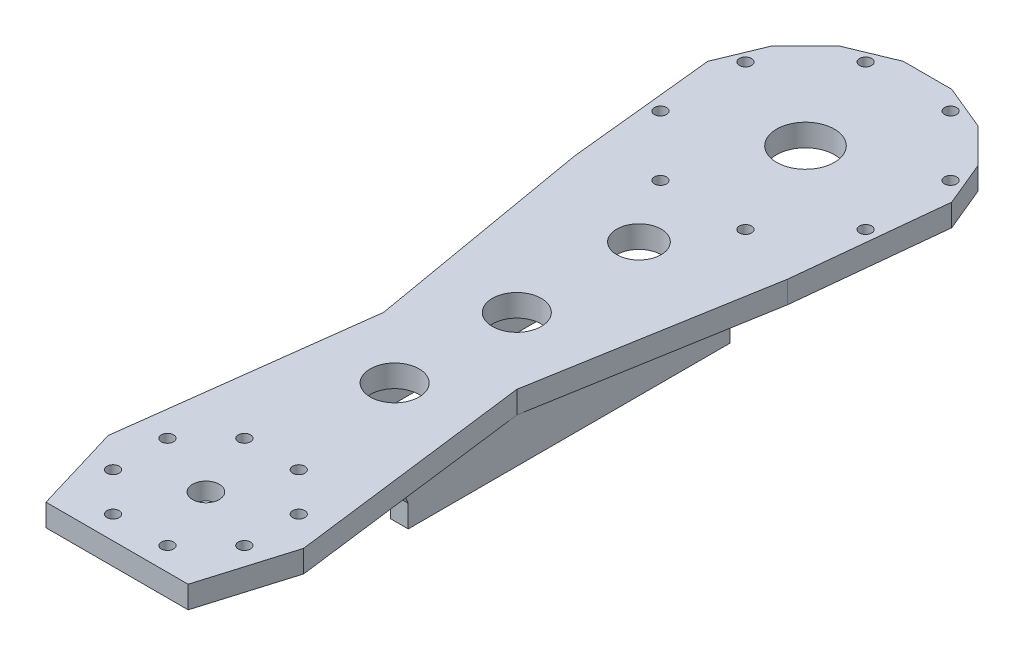
SolidWorks part; units mm, degrees
material "6061-T6 (SS)"
ref_plane "Front Plane" through (0, 0, 0) normal (0, 0, 1) x (1, 0, 0)
ref_plane "Top Plane" through (0, 0, 0) normal (0, 1, 0) x (1, 0, 0)
ref_plane "Right Plane" through (0, 0, 0) normal (1, 0, 0) x (0, 0, -1)
ref_plane "PL_Thigh_Plate_base" through (0, 36, 0) normal (0, 1, 0) x (1, 0, 0)
sketch "SK_Thigh_Plate" plane through (0, 36, 0) normal (0, 1, 0) x (1, 0, 0)
  line L0 (-32, -40) -> (32, -40)
  line L1 (32, -40) -> (44, 0)
  line L2 (44, 0) -> (30, 110)
  line L3 (30, 110) -> (48, 214)
  line L4 (48, 214) -> (54.924, 280.9251)
  line L5 (54.924, 280.9251) -> (46.5623, 301.1119)
  line L6 (46.5623, 301.1119) -> (31.1119, 316.5623)
  line L7 (31.1119, 316.5623) -> (10.9251, 324.924)
  line L8 (10.9251, 324.924) -> (-10.9251, 324.924)
  line L9 (-10.9251, 324.924) -> (-31.1119, 316.5623)
  line L10 (-31.1119, 316.5623) -> (-46.5623, 301.1119)
  line L11 (-46.5623, 301.1119) -> (-54.924, 280.9251)
  line L12 (-54.924, 280.9251) -> (-48, 214)
  line L13 (-48, 214) -> (-30, 110)
  line L14 (-30, 110) -> (-44, 0)
  line L15 (-44, 0) -> (-32, -40)
  circle A0 centre (29.5641, 12.2459) radius 2.75
  circle A1 centre (12.2459, 29.5641) radius 2.75
  circle A2 centre (-12.2459, 29.5641) radius 2.75
  circle A3 centre (-29.5641, 12.2459) radius 2.75
  circle A4 centre (-29.5641, -12.2459) radius 2.75
  circle A5 centre (-12.2459, -29.5641) radius 2.75
  circle A6 centre (12.2459, -29.5641) radius 2.75
  circle A7 centre (29.5641, -12.2459) radius 2.75
  circle A8 centre (46.194, 289.1342) radius 2.75
  circle A9 centre (19.1342, 316.194) radius 2.75
  circle A10 centre (-19.1342, 316.194) radius 2.75
  circle A11 centre (-46.194, 289.1342) radius 2.75
  circle A12 centre (-46.194, 250.8658) radius 2.75
  circle A13 centre (-19.1342, 223.806) radius 2.75
  circle A14 centre (19.1342, 223.806) radius 2.75
  circle A15 centre (46.194, 250.8658) radius 2.75
  circle A16 centre (0, 0) radius 6
  circle A17 centre (0, 270) radius 13
  circle A18 centre (0, 85) radius 11
  circle A19 centre (0, 140) radius 11
  circle A20 centre (0, 195) radius 10
  dimension "D31_SK_Thigh_Plate" = 5.5
  dimension "D34_SK_Thigh_Plate" = 5.5
  dimension "D37_SK_Thigh_Plate" = 5.5
  dimension "D40_SK_Thigh_Plate" = 5.5
  dimension "D43_SK_Thigh_Plate" = 5.5
  dimension "D46_SK_Thigh_Plate" = 5.5
  dimension "D49_SK_Thigh_Plate" = 5.5
  dimension "D52_SK_Thigh_Plate" = 5.5
  dimension "D55_SK_Thigh_Plate" = 5.5
  dimension "D58_SK_Thigh_Plate" = 5.5
  dimension "D61_SK_Thigh_Plate" = 5.5
  dimension "D64_SK_Thigh_Plate" = 5.5
  dimension "D67_SK_Thigh_Plate" = 5.5
  dimension "D70_SK_Thigh_Plate" = 5.5
  dimension "D73_SK_Thigh_Plate" = 5.5
  dimension "D76_SK_Thigh_Plate" = 5.5
  dimension "D79_SK_Thigh_Plate" = 12
  dimension "D80_SK_Thigh_Plate" = 26
  dimension "D82_SK_Thigh_Plate" = 22
  dimension "D84_SK_Thigh_Plate" = 22
  dimension "D86_SK_Thigh_Plate" = 20
  dimension "P1" = 32
  dimension "P2" = 40
  dimension "P3" = 32
  dimension "P4" = 40
  dimension "P5" = 44
  dimension "P6" = 30
  dimension "P7" = 110
  dimension "P8" = 48
  dimension "P9" = 214
  dimension "P10" = 54.924
  dimension "P11" = 280.9251
  dimension "P12" = 46.5623
  dimension "P13" = 301.1119
  dimension "P14" = 31.1119
  dimension "P15" = 316.5623
  dimension "P16" = 10.9251
  dimension "P17" = 324.924
  dimension "P18" = 10.9251
  dimension "P19" = 324.924
  dimension "P20" = 31.1119
  dimension "P21" = 316.5623
  dimension "P22" = 46.5623
  dimension "P23" = 301.1119
  dimension "P24" = 54.924
  dimension "P25" = 280.9251
  dimension "P26" = 48
  dimension "P27" = 214
  dimension "P28" = 30
  dimension "P29" = 110
  dimension "P30" = 44
  dimension "P32" = 29.5641
  dimension "P33" = 12.2459
  dimension "P35" = 12.2459
  dimension "P36" = 29.5641
  dimension "P38" = 12.2459
  dimension "P39" = 29.5641
  dimension "P41" = 29.5641
  dimension "P42" = 12.2459
  dimension "P44" = 29.5641
  dimension "P45" = 12.2459
  dimension "P47" = 12.2459
  dimension "P48" = 29.5641
  dimension "P50" = 12.2459
  dimension "P51" = 29.5641
  dimension "P53" = 29.5641
  dimension "P54" = 12.2459
  dimension "P56" = 46.194
  dimension "P57" = 289.1342
  dimension "P59" = 19.1342
  dimension "P60" = 316.194
  dimension "P62" = 19.1342
  dimension "P63" = 316.194
  dimension "P65" = 46.194
  dimension "P66" = 289.1342
  dimension "P68" = 46.194
  dimension "P69" = 250.8658
  dimension "P71" = 19.1342
  dimension "P72" = 223.806
  dimension "P74" = 19.1342
  dimension "P75" = 223.806
  dimension "P77" = 46.194
  dimension "P78" = 250.8658
  dimension "P81" = 270
  dimension "P83" = 85
  dimension "P85" = 140
  dimension "P87" = 195
extrude "Thigh_Plate" add sketch "SK_Thigh_Plate" along normal blind 10
ref_plane "PL_Pitch_Pilot_Recess_base" through (0, 36, 0) normal (0, 1, 0) x (1, 0, 0)
sketch "SK_Pitch_Pilot_Recess" plane through (0, 36, 0) normal (0, 1, 0) x (1, 0, 0)
  circle A0 centre (0, 0) radius 25.15
  dimension "D1_SK_Pitch_Pilot_Recess" = 50.3
extrude "Pitch_Pilot_Recess" cut sketch "SK_Pitch_Pilot_Recess" along normal blind 2.2
ref_plane "PL_Front_Flange_base" through (22, 0, 0) normal (1, 0, 0) x (0, 0, -1)
sketch "SK_Front_Flange" plane through (22, 0, 0) normal (1, 0, 0) x (0, 0, -1)
  line L0 (35.5977, 31) -> (35.5977, 36)
  line L1 (35.5977, 36) -> (206, 36)
  line L2 (206, 36) -> (206, 16)
  line L3 (206, 16) -> (61.0999, 16)
  line L4 (61.0999, 16) -> (61.0999, 26)
  line L5 (61.0999, 26) -> (59.0999, 31)
  line L6 (59.0999, 31) -> (35.5977, 31)
  dimension "P1" = 35.5977
  dimension "P2" = 31
  dimension "P3" = 35.5977
  dimension "P4" = 36
  dimension "P5" = 206
  dimension "P6" = 36
  dimension "P7" = 206
  dimension "P8" = 16
  dimension "P9" = 61.0999
  dimension "P10" = 16
  dimension "P11" = 61.0999
  dimension "P12" = 26
  dimension "P13" = 59.0999
  dimension "P14" = 31
extrude "Front_Flange" add sketch "SK_Front_Flange" along normal blind 8
ref_plane "PL_Back_Flange_base" through (-30, 0, 0) normal (1, 0, 0) x (0, 0, -1)
sketch "SK_Back_Flange" plane through (-30, 0, 0) normal (1, 0, 0) x (0, 0, -1)
  line L0 (35.5977, 31) -> (35.5977, 36)
  line L1 (35.5977, 36) -> (206, 36)
  line L2 (206, 36) -> (206, 16)
  line L3 (206, 16) -> (61.0999, 16)
  line L4 (61.0999, 16) -> (61.0999, 26)
  line L5 (61.0999, 26) -> (59.0999, 31)
  line L6 (59.0999, 31) -> (35.5977, 31)
  dimension "P1" = 35.5977
  dimension "P2" = 31
  dimension "P3" = 35.5977
  dimension "P4" = 36
  dimension "P5" = 206
  dimension "P6" = 36
  dimension "P7" = 206
  dimension "P8" = 16
  dimension "P9" = 61.0999
  dimension "P10" = 16
  dimension "P11" = 61.0999
  dimension "P12" = 26
  dimension "P13" = 59.0999
  dimension "P14" = 31
extrude "Back_Flange" add sketch "SK_Back_Flange" along normal blind 8
ref_axis "AX_PitchY" through (0, 47.5, 0) along (0, -1, 0)
ref_plane "PL_PitchRef" through (0, 0, 0) normal (-0.6428, 0, 0.766) x (0, -1, 0)
equation "\"Thigh_length\"= 270"
equation "\"Thigh_plate_t\"= 10"
equation "\"Flange_end_z\"= -206"
equation "\"Flange_deep_start_z\"= -61.0999"
equation "\"Flange_shallow_start_z\"= -35.5977"
